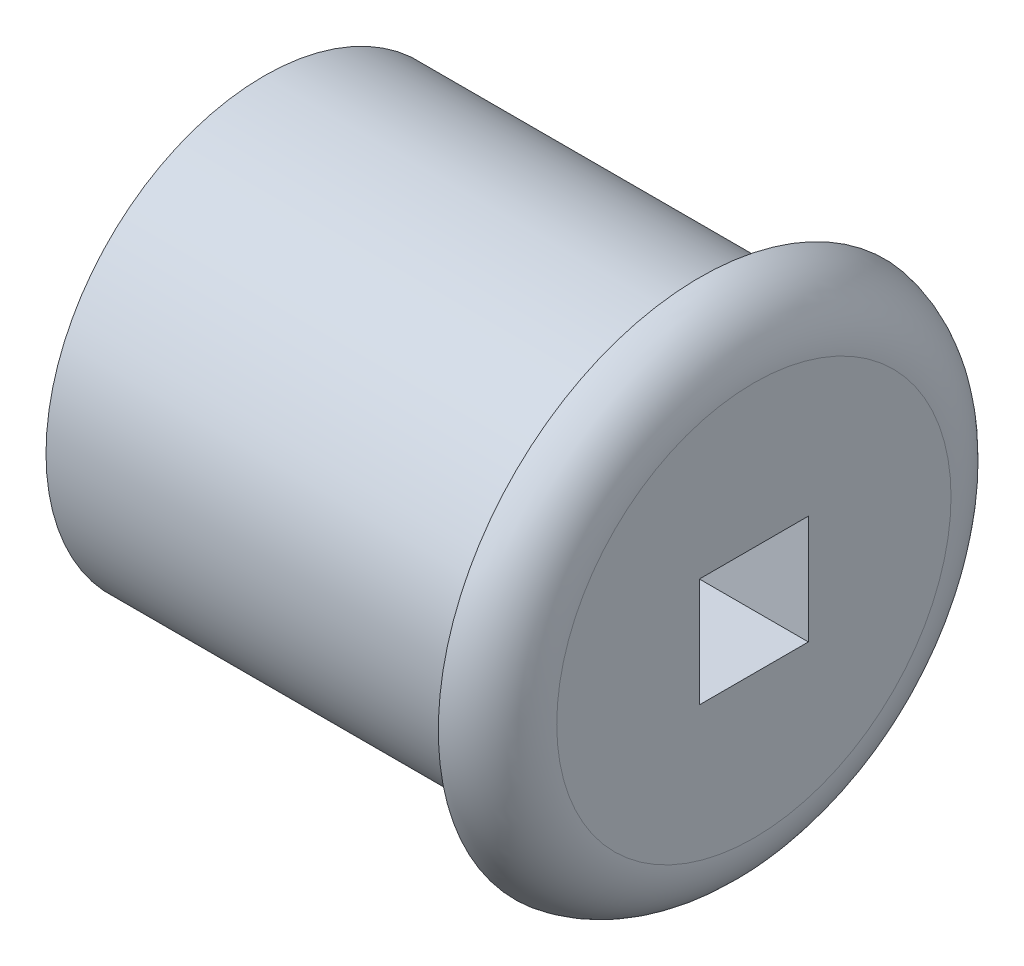
SolidWorks part; units mm, degrees
ref_plane "Front Plane" through (0, 0, 0) normal (0, 0, 1) x (1, 0, 0)
ref_plane "Top Plane" through (0, 0, 0) normal (0, 1, 0) x (1, 0, 0)
ref_plane "Right Plane" through (0, 0, 0) normal (1, 0, 0) x (0, 0, -1)
sketch "Sketch1" plane through (0, 0, 0) normal (1, 0, 0) x (0, 0, -1)
  circle A0 centre (0, 0) radius 12.7
  dimension "D1" = 25.4
extrude "Boss-Extrude1" add sketch "Sketch1" along normal blind 25.4
sketch "Sketch2" plane through (25.4, 0, 0) normal (1, 0, 0) x (0, 0, -1)
  circle A0 centre (0, 0) radius 15.24
  dimension "D1" = 30.48
extrude "Boss-Extrude2" add sketch "Sketch2" along normal blind 3.1496
fillet "Fillet1" radius 3.81 1 edges at (28.5496, 0, -15.24)
sketch "Sketch5" plane through (28.5496, 0, 0) normal (1, 0, 0) x (0, 0, -1)
  line L1 (-3.175, -3.175) -> (3.175, -3.175)
  line L2 (-3.175, -3.175) -> (-3.175, 3.175)
  line L3 (-3.175, 3.175) -> (3.175, 3.175)
  line L4 (3.175, -3.175) -> (3.175, 3.175)
  line L5 (-3.175, -3.175) -> (3.175, 3.175) construction
  line L6 (-3.175, 3.175) -> (3.175, -3.175) construction
  point P0 (0, 0)
  dimension "D1" = 6.35
extrude "Cut-Extrude2" cut sketch "Sketch5" against normal blind 12.7
